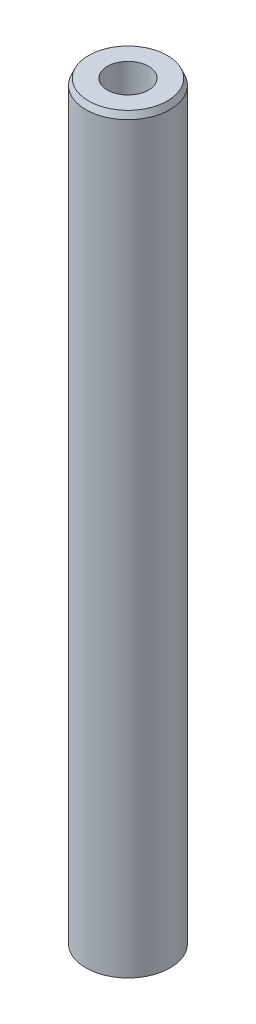
SolidWorks part; units mm, degrees
ref_plane "Front Plane" through (0, 0, 0) normal (0, 0, 1) x (1, 0, 0)
ref_plane "Top Plane" through (0, 0, 0) normal (0, 1, 0) x (1, 0, 0)
ref_plane "Right Plane" through (0, 0, 0) normal (1, 0, 0) x (0, 0, -1)
sketch "Sketch1" plane through (0, 0, 0) normal (0, 1, 0) x (1, 0, 0)
  circle A0 centre (0, 0) radius 12.5
  dimension "SHAFT_OD" = 25
extrude "Boss-Extrude1" add sketch "Sketch1" along normal blind 223.2787
sketch "Sketch2" plane through (0, 0, 0) normal (0, 1, 0) x (1, 0, 0)
  circle A0 centre (0, 0) radius 6.1144
  dimension "BORE_D" = 12.2288
extrude "Cut-Extrude1" cut sketch "Sketch2" along normal through all
chamfer "Chamfer1" distance 1.834 angle 23.561 2 edges at (0, 223.2787, 12.5) (0, 0, 12.5) first distance on face at (0, 223.2787, 12.5) first distance on face at (0, 0, 6.1144)
